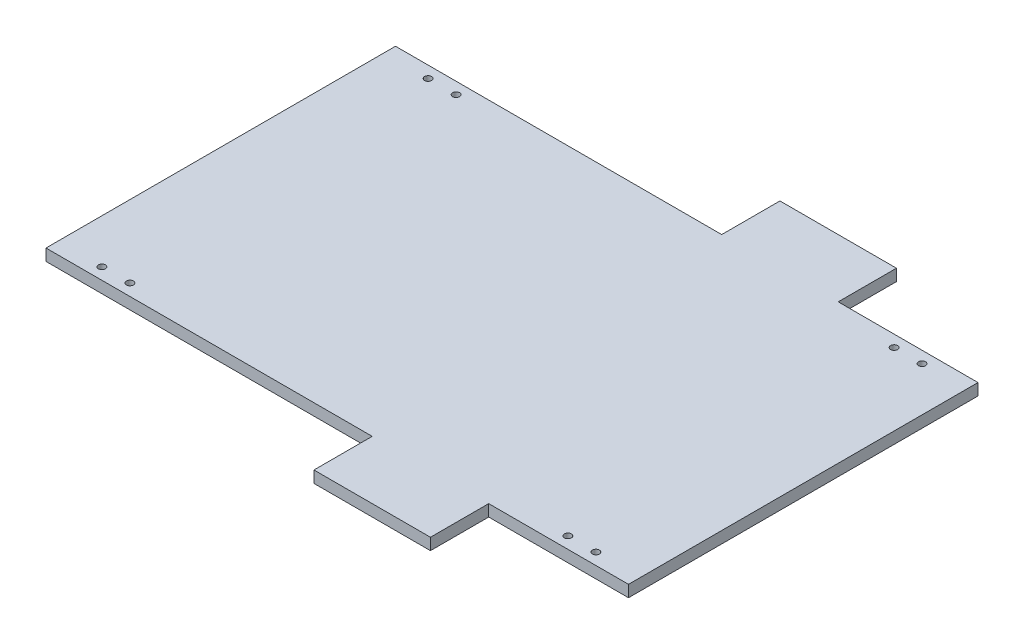
SolidWorks part; units mm, degrees
ref_plane "正面" through (0, 0, 0) normal (0, 0, 1) x (1, 0, 0)
ref_plane "平面" through (0, 0, 0) normal (0, 1, 0) x (1, 0, 0)
ref_plane "右側面" through (0, 0, 0) normal (1, 0, 0) x (0, 0, -1)
sketch "ｽｹｯﾁ1" plane through (0, 0, 0) normal (0, 1, 0) x (1, 0, 0)
  line L1 (125, -75) -> (-125, -75)
  line L2 (125, -75) -> (125, 75)
  line L3 (125, 75) -> (-125, 75)
  line L4 (-125, -75) -> (-125, 75)
  line L5 (125, -75) -> (-125, 75) construction
  line L6 (125, 75) -> (-125, -75) construction
  point P0 (0, 0)
  dimension "D1" = 250
  dimension "D2" = 150
extrude "ﾎﾞｽ - 押し出し1" add sketch "ｽｹｯﾁ1" along normal blind 5
sketch "ｽｹｯﾁ2" plane through (0, 5, 0) normal (0, 1, 0) x (1, 0, 0)
  line L0 (-125, 0) -> (0, 0) construction
  line L5 (-125, 75) -> (-125, -75) construction
  line L7 (0, 0) -> (0, 75) construction
  line L8 (125, 75) -> (-125, 75) construction
  line L9 (-106, 70) -> (-94, 70) construction
  line L10 (-106, -70) -> (-94, -70) construction
  line L11 (106, 70) -> (94, 70) construction
  line L12 (106, -70) -> (94, -70) construction
  circle A0 centre (-106, 70) radius 1.5
  circle A1 centre (-94, 70) radius 1.5
  circle A2 centre (-94, -70) radius 1.5
  circle A3 centre (-106, -70) radius 1.5
  circle A4 centre (94, 70) radius 1.5
  circle A5 centre (106, 70) radius 1.5
  circle A6 centre (94, -70) radius 1.5
  circle A7 centre (106, -70) radius 1.5
  point P24 (-100, 70)
  point P25 (100, 70)
  dimension "D1" = 3
  dimension "D2" = 12
  dimension "D3" = 5
  dimension "D4" = 200
extrude "ｶｯﾄ - 押し出し1" cut sketch "ｽｹｯﾁ2" against normal through all
sketch "ｽｹｯﾁ3" plane through (0, 5, 0) normal (0, 1, 0) x (1, 0, 0)
  line L0 (-125, -75) -> (125, -75) construction
  line L1 (65, 100) -> (15, 100)
  line L2 (65, 100) -> (65, 75)
  line L3 (65, -100) -> (15, -100)
  line L4 (15, 100) -> (15, 75)
  line L5 (65, 100) -> (15, -100) construction
  line L6 (65, -100) -> (15, 100) construction
  line L7 (15, 75) -> (65, 75)
  line L8 (125, 75) -> (-125, 75) construction
  line L9 (15, -75) -> (15, -100)
  line L10 (15, -75) -> (65, -75)
  line L11 (15, 75) -> (15, -75) construction
  line L12 (65, -75) -> (65, -100)
  line L13 (65, 75) -> (65, -75) construction
  line L14 (0, 0) -> (40, 0) construction
  point P0 (0, 0)
  point P14 (0, 0)
  point P15 (0, 0)
  point P18 (40, 0)
  dimension "D1" = 50
  dimension "D2" = 25
  dimension "D3" = 40
extrude "ﾎﾞｽ - 押し出し2" add sketch "ｽｹｯﾁ3" against normal up to surface (5 mm away) up to face at (94, 0, -71.5)
